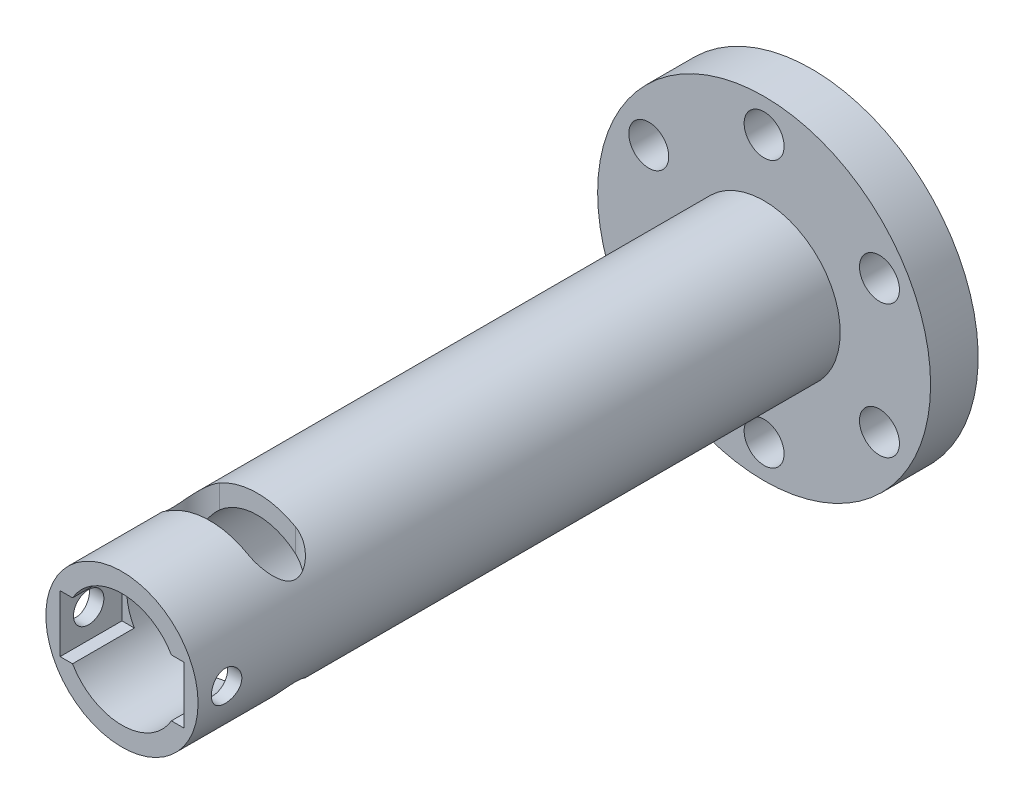
SolidWorks part; units mm, degrees
ref_plane "前视基准面" through (0, 0, 0) normal (0, 0, 1) x (1, 0, 0)
ref_plane "上视基准面" through (0, 0, 0) normal (0, 1, 0) x (1, 0, 0)
ref_plane "右视基准面" through (0, 0, 0) normal (1, 0, 0) x (0, 0, -1)
other "Configuration Table"
sketch "草图1" plane through (0, 0, 0) normal (0, 0, 1) x (1, 0, 0)
  circle A0 centre (0, 0) radius 17.5
  circle A2 centre (0, 14) radius 2
  circle A3 centre (12.1244, 7) radius 2
  circle A4 centre (12.1244, -7) radius 2
  circle A5 centre (0, -14) radius 2
  circle A6 centre (-12.1244, -7) radius 2
  circle A7 centre (-12.1244, 7) radius 2
  point P18 (0, 0)
  dimension "D1" = 35
  dimension "D2" = 6
extrude "凸台-拉伸1" add sketch "草图1" along normal blind 2
sketch "草图2" plane through (0, 0, 2) normal (0, 0, 1) x (1, 0, 0)
  circle A0 centre (0, 0) radius 8
extrude "凸台-拉伸2" add sketch "草图2" along normal blind 61.5
sketch "草图6" plane through (0, 0, 63.5) normal (0, 0, 1) x (1, 0, 0)
  circle A0 centre (0, 0) radius 8
extrude "凸台-拉伸3" add sketch "草图6" along normal blind 2
sketch "草图7" plane through (0, 0, 65.5) normal (0, 0, 1) x (1, 0, 0)
  circle A0 centre (0, 0) radius 5
extrude "切除-拉伸2" cut sketch "草图7" against normal up to surface (63.5 mm away) up to face at (8, 0, 2)
sketch "草图21" plane through (0, 0, 65.5) normal (0, 0, 1) x (1, 0, 0)
  circle A0 centre (0, 0) radius 7
extrude "切除-拉伸4" cut sketch "草图21" against normal up to surface (63.5 mm away) up to face at (8, 0, 2)
sketch "草图22" plane through (0, 0, 0) normal (0, 0, -1) x (-1, 0, 0)
  arc A1 (2, 5) -> (2, -5) centre (-3, 0) cw construction
  arc A2 (2.9997, -5.9997) -> (2.9997, 5.9997) centre (-3, 0) ccw
  arc A3 (1.0003, -4.0003) -> (1.0003, 4.0003) centre (-3, 0) ccw
  arc A4 (1.0003, -4.0003) -> (2.9997, -5.9997) centre (2, -5) ccw
  arc A5 (2.9997, 5.9997) -> (1.0003, 4.0003) centre (2, 5) ccw
  arc A6 (-2, -5) -> (-2, 5) centre (3, 0) cw construction
  arc A7 (-2.9997, 5.9997) -> (-2.9997, -5.9997) centre (3, 0) ccw
  arc A8 (-1.0003, 4.0003) -> (-1.0003, -4.0003) centre (3, 0) ccw
  arc A9 (-1.0003, 4.0003) -> (-2.9997, 5.9997) centre (-2, 5) ccw
  arc A10 (-2.9997, -5.9997) -> (-1.0003, -4.0003) centre (-2, -5) ccw
  point P5 (0, 0)
  point P11 (0, 0)
  point P14 (4.0711, 0)
  point P24 (-4.0711, 0)
  point P29 (0, 0)
  dimension "D1" = 2
extrude "切除-拉伸5" cut sketch "草图22" against normal up to surface (2 mm away) up to face at (8, 0, 2)
sketch "草图30" plane through (0, 0, 65.5) normal (0, 0, 1) x (1, 0, 0)
  circle A0 centre (0, 0) radius 8
extrude "切除-拉伸7" cut sketch "草图30" against normal blind 18
sketch "草图35" plane through (0, 0, 0) normal (0, 0, -1) x (-1, 0, 0)
  circle A0 centre (0, 14) radius 2.1
  circle A1 centre (12.1244, 7) radius 2.1
  circle A2 centre (12.1244, -7) radius 2.1
  circle A3 centre (0, -14) radius 2.1
  circle A4 centre (-12.1244, -7) radius 2.1
  circle A5 centre (-12.1244, 7) radius 2.1
  point P15 (0, 0)
  dimension "D1" = 6
extrude "切除-拉伸9" cut sketch "草图35" against normal blind 10
sketch "草图37" plane through (0, 0, 0) normal (0, 0, -1) x (-1, 0, 0)
  arc A0 (-2.9997, -5.9997) -> (-1.0003, -4.0003) centre (-2, -5) ccw construction
  circle A1 centre (0, 0) radius 17.5
  circle A2 centre (0, 0) radius 17.5
  arc A3 (-2.9997, 5.9997) -> (-2.9997, -5.9997) centre (3, 0) ccw construction
  arc A4 (-1.0003, 4.0003) -> (-1.0003, -4.0003) centre (3, 0) ccw construction
  arc A5 (-1.0003, 4.0003) -> (-2.9997, 5.9997) centre (-2, 5) ccw construction
  arc A6 (1.0003, -4.0003) -> (2.9997, -5.9997) centre (2, -5) ccw construction
  arc A7 (2.9997, 5.9997) -> (1.0003, 4.0003) centre (2, 5) ccw construction
  arc A8 (2.9997, -5.9997) -> (2.9997, 5.9997) centre (-3, 0) ccw construction
  arc A9 (1.0003, -4.0003) -> (1.0003, 4.0003) centre (-3, 0) ccw construction
  circle A10 centre (12.1244, 7) radius 2.1 construction
  circle A11 centre (12.1244, -7) radius 2.1 construction
  circle A12 centre (0, -14) radius 2.1 construction
  circle A13 centre (-12.1244, -7) radius 2.1 construction
  circle A14 centre (-12.1244, 7) radius 2.1 construction
  circle A15 centre (0, 14) radius 2.1 construction
  arc A16 (-2.9997, -5.9997) -> (-1.0003, -4.0003) centre (-2, -5) ccw
  arc A17 (-2.9997, 5.9997) -> (-2.9997, -5.9997) centre (3, 0) ccw
  arc A18 (-1.0003, 4.0003) -> (-1.0003, -4.0003) centre (3, 0) ccw
  arc A19 (-1.0003, 4.0003) -> (-2.9997, 5.9997) centre (-2, 5) ccw
  arc A20 (1.0003, -4.0003) -> (2.9997, -5.9997) centre (2, -5) ccw
  arc A21 (2.9997, 5.9997) -> (1.0003, 4.0003) centre (2, 5) ccw
  arc A22 (2.9997, -5.9997) -> (2.9997, 5.9997) centre (-3, 0) ccw
  arc A23 (1.0003, -4.0003) -> (1.0003, 4.0003) centre (-3, 0) ccw
  circle A24 centre (12.1244, 7) radius 2.1
  circle A25 centre (12.1244, -7) radius 2.1
  circle A26 centre (0, -14) radius 2.1
  circle A27 centre (-12.1244, -7) radius 2.1
  circle A28 centre (-12.1244, 7) radius 2.1
  circle A29 centre (0, 14) radius 2.1
  dimension "D1" = 0
extrude "凸台-拉伸5" add sketch "草图37" along normal blind 3
sketch "草图44" plane through (0, 0, 47.5) normal (0, 0, 1) x (1, 0, 0)
  circle A0 centre (0, 0) radius 8
  circle A1 centre (0, 0) radius 6
extrude "凸台-拉伸7" add sketch "草图44" along normal blind 10 and the other way blind 46
sketch "草图45" plane through (0, 0, 57.5) normal (0, 0, 1) x (1, 0, 0)
  point P3 (-6, 0)
sketch "草图46" plane through (0, 0, 57.5) normal (0, 0, 1) x (1, 0, 0)
  line L0 (0, -3) -> (0, 3)
  line L1 (0, 3) -> (-6.5, 3)
  line L2 (-6.5, 3) -> (-6.5, -3)
  line L3 (-6.5, -3) -> (0, -3)
  line L4 (0, -3) -> (6.5, -3)
  line L5 (0, 3) -> (6.5, 3)
  line L6 (6.5, 3) -> (6.5, -3)
  point P6 (0, 0)
  circle M8 centre (0, 0) radius 6
extrude "切除-拉伸21" cut sketch "草图46" against normal up to surface (55.5 mm away) contours L2 L3 L1 M8 | L3 L0 L1 M8 | L5 L0 L4 M8 | L6 L5 L4 M8 region at (-2.8747, 0, 57.5) region at (2.8747, 0, 57.5) region at (-6.0829, 0, 57.5) region at (6.0829, 0, 57.5) up to face at (2.1, 14, 2)
sketch "草图47" plane through (0, 0, 57.5) normal (0, 0, 1) x (1, 0, 0)
  line L0 (5.1962, -3) -> (6.5, -3) construction
  line L1 (6.5, -3) -> (6.5, 3) construction
  line L2 (5.1962, 3) -> (6.5, 3) construction
  line L3 (-5.1962, -3) -> (-6.5, -3) construction
  line L4 (-6.5, 3) -> (-6.5, -3) construction
  line L5 (-5.1962, 3) -> (-6.5, 3) construction
  line L6 (5.1962, -3) -> (6.5, -3)
  line L7 (6.5, -3) -> (6.5, 3)
  line L8 (5.1962, 3) -> (6.5, 3)
  line L9 (-5.1962, -3) -> (-6.5, -3)
  line L10 (-6.5, 3) -> (-6.5, -3)
  line L11 (-5.1962, 3) -> (-6.5, 3)
  circle A0 centre (0, 0) radius 8
  arc A1 (-5.1962, -3) -> (5.1962, -3) centre (0, 0) ccw construction
  arc A2 (5.1962, 3) -> (-5.1962, 3) centre (0, 0) ccw construction
  arc A3 (-5.1962, -3) -> (5.1962, -3) centre (0, 0) ccw
  arc A4 (5.1962, 3) -> (-5.1962, 3) centre (0, 0) ccw
extrude "凸台-拉伸8" add sketch "草图47" along normal blind 5
sketch "草图48" plane through (0, 0, 62.5) normal (0, 0, 1) x (1, 0, 0)
  line L0 (-5.1962, -3) -> (-6.5, -3) construction
  line L1 (5.1962, -3) -> (6.5, -3) construction
  line L2 (6.5, -3) -> (6.5, 3) construction
  line L3 (5.1962, 3) -> (6.5, 3) construction
  line L4 (-6.5, 3) -> (-5.1962, 3) construction
  line L5 (-6.5, 3) -> (-6.5, -3) construction
  line L6 (-5.1962, -3) -> (-6.5, -3)
  line L7 (5.1962, -3) -> (6.5, -3)
  line L8 (6.5, -3) -> (6.5, 3)
  line L9 (5.1962, 3) -> (6.5, 3)
  line L10 (-6.5, 3) -> (-5.1962, 3)
  line L11 (-6.5, 3) -> (-6.5, -3)
  circle A0 centre (0, 0) radius 8
  arc A1 (-5.1962, -3) -> (5.1962, -3) centre (0, 0) ccw construction
  arc A2 (5.1962, 3) -> (-5.1962, 3) centre (0, 0) ccw construction
  arc A3 (-5.1962, -3) -> (5.1962, -3) centre (0, 0) ccw
  arc A4 (5.1962, 3) -> (-5.1962, 3) centre (0, 0) ccw
extrude "凸台-拉伸9" add sketch "草图48" along normal blind 7
sketch "草图49" plane through (0, 0, 0) normal (1, 0, 0) x (0, 0, -1)
  line L0 (-69.5, 0) -> (-66.5, 0)
  line L1 (-69.5, 8) -> (-69.5, -8) construction
  circle A0 centre (-66.5, 0) radius 1.6
  dimension "D1" = 3.2
extrude "切除-拉伸22" cut sketch "草图49" against normal blind 11 and the other way blind 21 contours A0 region at (0, -1.5547, 66.5)
sketch "草图52" plane through (0, 0, 2) normal (0, 0, 1) x (1, 0, 0)
  circle A0 centre (0, 0) radius 6.7989
extrude "切除-拉伸25" cut sketch "草图52" against normal blind 10
sketch "草图53" plane through (0, 0, 2) normal (0, 0, -1) x (-1, 0, 0)
  circle A0 centre (0, 0) radius 6.7989
  circle A1 centre (0, 0) radius 6
extrude "凸台-拉伸11" add sketch "草图53" along normal up to surface (5 mm away) contours A0 | A1 up to face at (-6.7989, 0, -3)
sketch "草图56" plane through (0, 0, 0) normal (0, 1, 0) x (1, 0, 0)
  line L0 (0, 3) -> (0, -56)
  line L1 (6, 3) -> (-6, 3) construction
  line L2 (4, -57.7499) -> (-4, -57.7499) construction
  line L3 (4, -60.2499) -> (-4, -60.2499)
  line L4 (4, -55.2499) -> (-4, -55.2499)
  arc A0 (4, -60.2499) -> (4, -55.2499) centre (4, -57.7499) ccw
  arc A1 (-4, -55.2499) -> (-4, -60.2499) centre (-4, -57.7499) ccw
  point P6 (0, -57.7499)
extrude "切除-拉伸26" cut sketch "草图56" along normal blind 21 and the other way blind 29 contours L4 A1 L3 A0 region at (0, 0, 57.7499)
sketch "草图57" plane through (0, 0, 2) normal (0, 0, 1) x (1, 0, 0)
  line L0 (-5.1962, 3) -> (-6.5, 3)
  line L1 (-6.5, 3) -> (-6.5, -3)
  line L2 (-6.5, 3) -> (-6.5, -3) construction
  line L3 (-6.5, -3) -> (-6.5, 3) construction
  line L4 (-6.5, -3) -> (-5.1962, -3)
  line L5 (5.1962, 3) -> (6.5, 3)
  line L6 (6.5, 3) -> (6.5, -3)
  line L7 (6.5, -3) -> (5.1962, -3)
  circle A1 centre (0, 0) radius 6
  line M2 (-6.5, 3) -> (-6.5, -3)
  line M3 (-6.5, -3) -> (-5.1962, -3)
  arc M4 (-5.1962, -3) -> (-5.1962, 3) centre (0, 0) cw
  line M5 (-5.1962, 3) -> (-6.5, 3)
extrude "凸台-拉伸13" add sketch "草图57" along normal blind 61 contours M5 M2 M3 M4 | A1 L7 L6 L5 region at (-6.0829, 0, 2) region at (6.0829, 0, 2)
